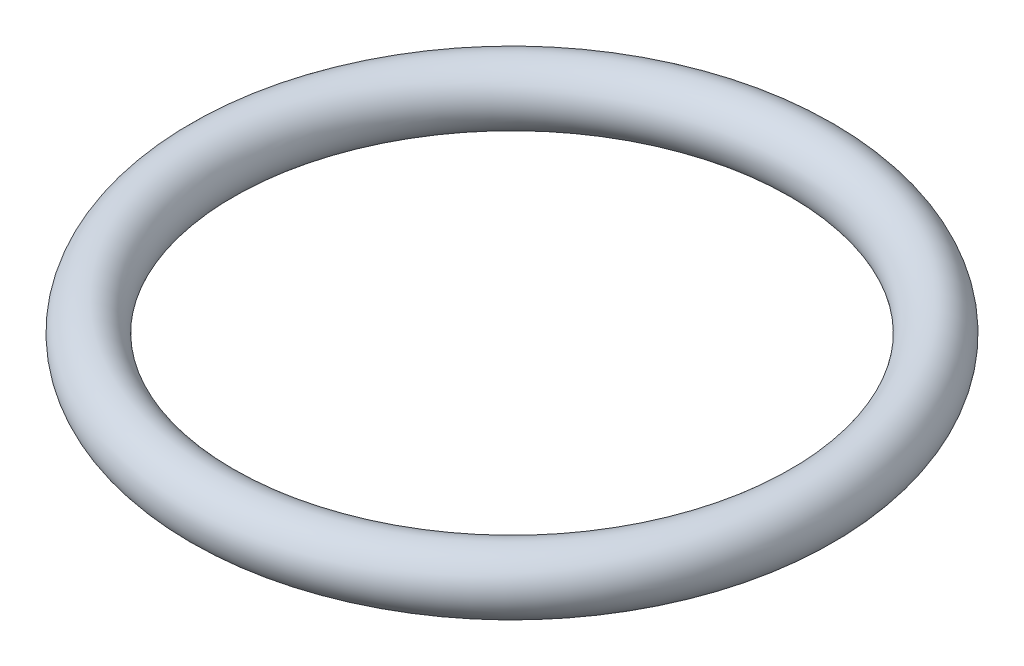
SolidWorks part; units mm, degrees
ref_plane "Front Plane" through (0, 0, 0) normal (0, 0, 1) x (1, 0, 0)
ref_plane "Top Plane" through (0, 0, 0) normal (0, 1, 0) x (1, 0, 0)
ref_plane "Right Plane" through (0, 0, 0) normal (1, 0, 0) x (0, 0, -1)
sketch "Sketch1" plane through (0, 0, 0) normal (0, 0, 1) x (1, 0, 0)
  line L0 (0, -16.0339) -> (0, 22.4854) construction
  circle A0 centre (-12.7, 0) radius 1.27
  dimension "D1" = 2.54
  dimension "D2" = 12.7
revolve "Revolve1" add sketch "Sketch1" angle 360 about L0
ref_plane "Plane1" through (0, 1.27, 0) normal (0, 1, 0) x (-1, 0, 0)
ref_plane "Plane2" through (0, 0, 13.97) normal (0, 0, 1) x (1, 0, 0)
ref_axis "Axis1" through (-15.367, 1.27, 13.97) along (1, 0, 0)
